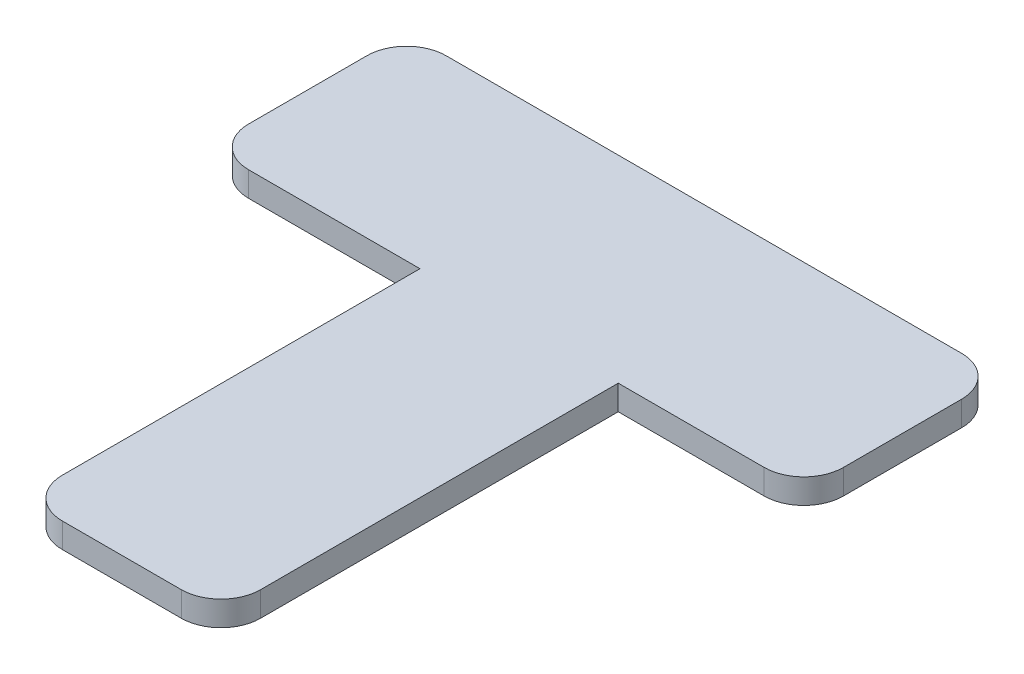
SolidWorks part; units mm, degrees
ref_plane "Front Plane" through (0, 0, 0) normal (0, 0, 1) x (1, 0, 0)
ref_plane "Top Plane" through (0, 0, 0) normal (0, 1, 0) x (1, 0, 0)
ref_plane "Right Plane" through (0, 0, 0) normal (1, 0, 0) x (0, 0, -1)
sketch "Sketch1" plane through (0, 0, 0) normal (0, 1, 0) x (1, 0, 0)
  line L0 (25.4, 50.8958) -> (49.1706, 50.8958)
  line L1 (0, 0) -> (25.4, 0)
  line L2 (0, 0) -> (0, 50.8958)
  line L4 (25.4, 0) -> (25.4, 50.8958)
  line L5 (-27.0294, 50.8958) -> (0, 50.8958)
  line L6 (-27.0294, 50.8958) -> (-27.0294, 76.2)
  line L7 (-27.0294, 76.2) -> (49.1706, 76.2)
  line L8 (49.1706, 50.8958) -> (49.1706, 76.2)
  dimension "D1" = 76.2
  dimension "D2" = 76.2
  dimension "D3" = 25.3042
  dimension "D4" = 25.4
extrude "Boss-Extrude1" add sketch "Sketch1" along normal blind 3.175
fillet "Fillet1" radius 5.08 6 edges at (-27.0294, 1.5875, -50.8958) (0, 1.5875, 0) (25.4, 1.5875, 0) (49.1706, 1.5875, -50.8958) (49.1706, 1.5875, -76.2) (-27.0294, 1.5875, -76.2)
